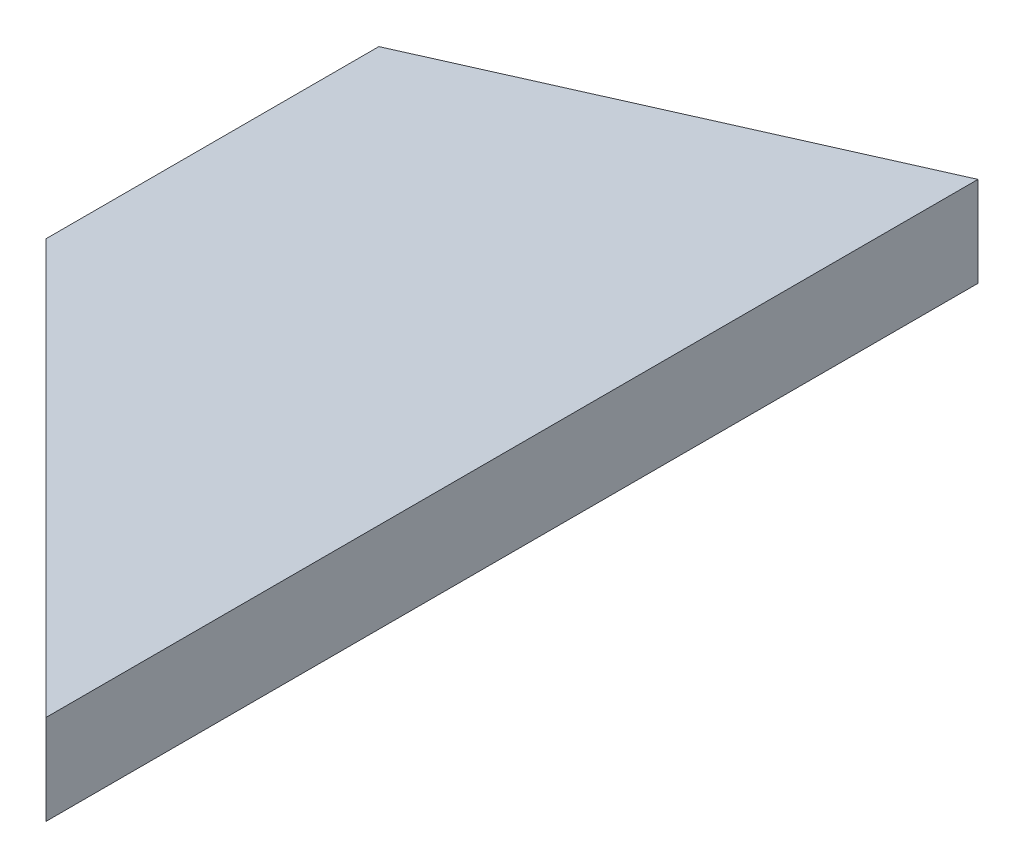
SolidWorks part; units mm, degrees
material "Pine"
ref_plane "Front Plane" through (0, 0, 0) normal (0, 0, 1) x (1, 0, 0)
ref_plane "Top Plane" through (0, 0, 0) normal (0, 1, 0) x (1, 0, 0)
ref_plane "Right Plane" through (0, 0, 0) normal (1, 0, 0) x (0, 0, -1)
sketch "Sketch1" plane through (0, 0, 0) normal (0, 0, 1) x (1, 0, 0)
  line L0 (0, 0) -> (0, 19.558)
  line L1 (0, 19.558) -> (28.575, 8.5891)
  line L2 (28.575, 8.5891) -> (28.575, 0)
  line L3 (28.575, 0) -> (0, 0)
  dimension "D1" = 19.558
  dimension "D2" = 28.575
  dimension "D3" = 21
extrude "Boss-Extrude1" add sketch "Sketch1" along normal blind 88.9
chamfer "Chamfer1" distance 28.575 angle 45 2 edges at (0, 9.779, 88.9) (0, 9.779, 0)
